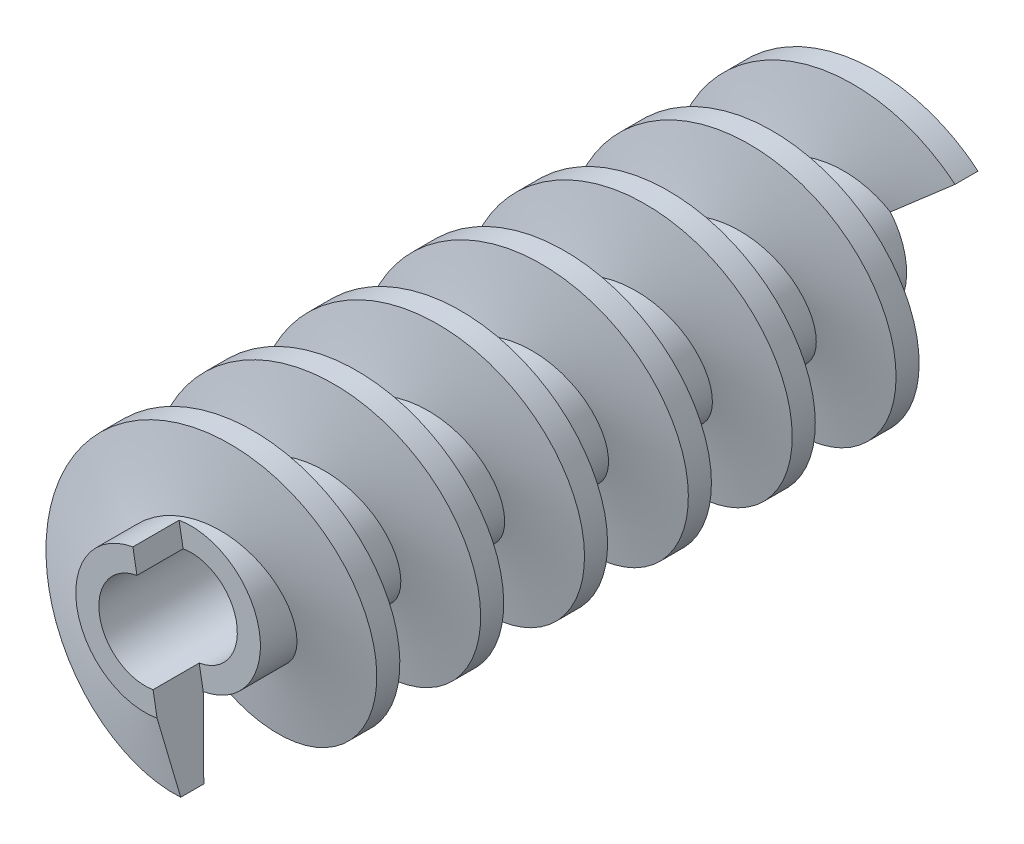
SolidWorks part; units mm, degrees
ref_plane "前视基准面" through (0, 0, 0) normal (0, 0, 1) x (1, 0, 0)
ref_plane "上视基准面" through (0, 0, 0) normal (0, 1, 0) x (1, 0, 0)
ref_plane "右视基准面" through (0, 0, 0) normal (1, 0, 0) x (0, 0, -1)
sketch "草图1" plane through (0, 0, 0) normal (0, 0, 1) x (1, 0, 0)
  circle A0 centre (0, 0) radius 2
  circle A1 centre (0, 0) radius 3
extrude "凸台-拉伸1" add sketch "草图1" against normal blind 32
sketch "草图3" plane through (0, 0, 0) normal (0, 0, 1) x (1, 0, 0)
  circle A0 centre (0, 0) radius 3
curve "螺旋线/涡状线1" pitch 4.5 height 31.5 radius 3 centre (0, 0, 0) axis (0, 0, -1) start towards (1, 0, 0)
sketch "草图4" plane through (0, 0, 0) normal (0, 1, 0) x (1, 0, 0)
  line L0 (3, 1) -> (3, -1)
  line L2 (6, 0.5) -> (6, -0.5)
  line L3 (3, -1) -> (6, -0.5)
  line L4 (3, 1) -> (6, 0.5)
sweep "扫描1" add profiles "草图4" path "螺旋线/涡状线1"
sketch "草图14" plane through (0, 0, 0) normal (0, 0, 1) x (1, 0, 0)
  circle A0 centre (0, 0) radius 7
  dimension "D1" = 14
extrude "切除-拉伸6" cut sketch "草图14" along normal blind 5
sketch "草图15" plane through (0, 0, 0) normal (0, 0, 1) x (1, 0, 0)
  line L0 (0, 0) -> (0.5236, -2.954)
  line L1 (0.5236, -2.954) -> (1.2216, -6.8926)
  line L2 (0, 0) -> (-1.2216, 6.8926)
  arc A0 (1.2216, -6.8926) -> (-1.2216, 6.8926) centre (0, 0) ccw
  dimension "D1" = 7
  dimension "D2" = 180
extrude "切除-拉伸7" cut sketch "草图15" against normal blind 2
sketch "草图16" plane through (0, 0, -32) normal (0, 0, -1) x (-1, 0, 0)
  circle A0 centre (0, 0) radius 7
  dimension "D1" = 14
extrude "切除-拉伸8" cut sketch "草图16" along normal blind 2
sketch "草图17" plane through (0, 0, -32) normal (0, 0, -1) x (-1, 0, 0)
  line L0 (0, 0) -> (-2.2964, 1.9304)
  line L1 (-2.2964, 1.9304) -> (-5.3583, 4.5043)
  line L2 (0, 0) -> (5.3583, -4.5043)
  arc A0 (-5.3583, 4.5043) -> (5.3583, -4.5043) centre (0, 0) ccw
  dimension "D1" = 7
  dimension "D2" = 180
extrude "切除-拉伸9" cut sketch "草图17" against normal blind 2
